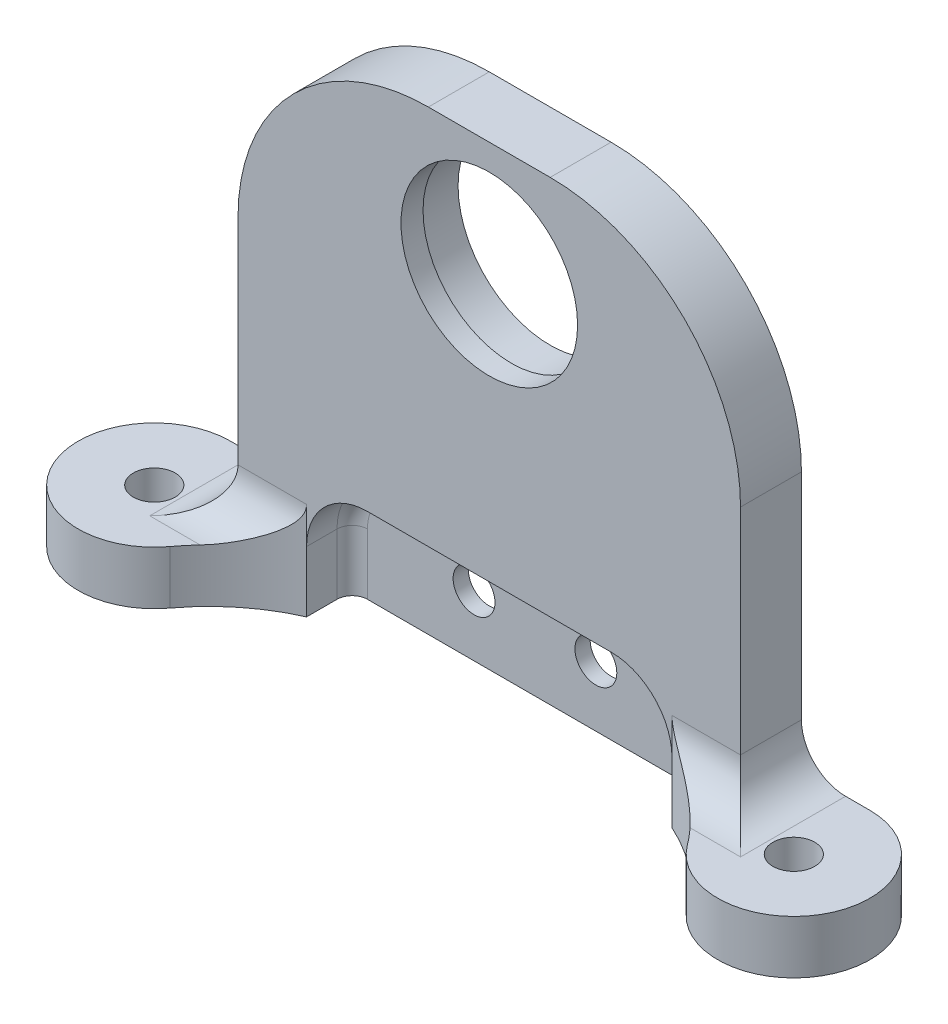
SolidWorks part; units mm, degrees
ref_plane "Front Plane" through (0, 0, 0) normal (0, 0, 1) x (1, 0, 0)
ref_plane "Top Plane" through (0, 0, 0) normal (0, 1, 0) x (1, 0, 0)
ref_plane "Right Plane" through (0, 0, 0) normal (1, 0, 0) x (0, 0, -1)
sketch "Sketch1" plane through (0, 0, 0) normal (0, 0, 1) x (1, 0, 0)
  line L1 (0, 15) -> (33, 15)
  line L2 (0, 15) -> (0, -51)
  line L3 (0, -51) -> (33, -51)
  line L4 (33, 15) -> (33, -51)
  point P5 (0, 0)
  dimension "D1" = 33
  dimension "D2" = 66
  dimension "D4" = 15
extrude "Boss-Extrude1" add sketch "Sketch1" along normal blind 8 separate body
sketch "Sketch3" plane through (0, 0, 8) normal (0, 0, 1) x (1, 0, 0)
  line L0 (0, 15) -> (0, -51) construction
  line L1 (33, 15) -> (0, 15) construction
  line L2 (9.5671, -23.097) -> (0, 0) construction
  line L3 (-17.5, 0) -> (-32.5, 0) construction
  line L4 (33, -51) -> (33, 15) construction
  line L5 (0, -51) -> (33, -51) construction
  circle A0 centre (25, -20) radius 2.75 construction
  circle A1 centre (0, 0) radius 11.6
  arc A2 (-17.5, 0) -> (6.697, -16.1679) centre (0, 0) ccw construction
  arc A3 (-32.5, 0) -> (12.4372, -30.0261) centre (0, 0) ccw construction
  arc A4 (12.4372, -30.0261) -> (6.697, -16.1679) centre (9.5671, -23.097) ccw construction
  dimension "D1" = 5.5
  dimension "D2" = 23.2
  dimension "D4" = 35
  dimension "D5" = 65
  dimension "D3" = 15
  dimension "D6" = 22.5
  dimension "D7" = 8
  dimension "D8" = 31
extrude "Cut-Extrude1" cut sketch "Sketch3" against normal through all
sketch "Sketch6" plane through (0, 0, 0) normal (0, 0, -1) x (-1, 0, 0)
  circle A0 centre (0, 0) radius 12.1
  dimension "D1" = 24.2
extrude "Cut-Extrude2" cut sketch "Sketch6" against normal blind 5.1
fillet "Fillet4" radius 25 1 edges at (33, 15, 4)
sketch "Sketch10" plane through (0, -51, 0) normal (0, -1, 0) x (1, 0, 0)
  line L0 (42, 0) -> (32, 0)
  line L1 (0, 0) -> (33, 0) construction
  line L2 (32, 10) -> (32, 0)
  line L3 (33, 8) -> (33, 0) construction
  arc A0 (42, 0) -> (32, 10) centre (42, 10) ccw
  circle A1 centre (42, 10) radius 2.75
  dimension "D1" = 5.5
  dimension "D2" = 20
  dimension "D3" = 1
extrude "Boss-Extrude4" add sketch "Sketch10" against normal blind 7
sketch "Sketch11" plane through (0, 0, 8) normal (0, 0, 1) x (1, 0, 0)
  line L1 (0, -51) -> (24, -51)
  line L2 (0, -51) -> (0, -35)
  line L3 (0, -35) -> (16, -35)
  line L4 (24, -51) -> (24, -43)
  arc A0 (16, -35) -> (24, -43) centre (16, -43) cw
  dimension "D1" = 8
  dimension "D2" = 16
  dimension "D3" = 24
extrude "Cut-Extrude3" cut sketch "Sketch11" against normal blind 6
sketch "Sketch12" plane through (0, 0, 2) normal (0, 0, 1) x (1, 0, 0)
  line L0 (8, -43) -> (0, -43) construction
  line L1 (0, -35) -> (0, -51) construction
  circle A0 centre (8, -43) radius 2.75
  dimension "D1" = 5.5
  dimension "D2" = 8
extrude "Cut-Extrude4" cut sketch "Sketch12" against normal blind 6
fillet "Fillet7" radius 2 3 edges at (24, -47, 2) (8, -35, 2) (21.6569, -37.3431, 2)
fillet "Fillet5" radius 25 1 edges at (32, -47.5, 8)
fillet "Fillet6" radius 5.8 2 edges at (33, -44, 4) (28.5, -44, 8)
mirror "Mirror1" about plane through (0, 15, 8) normal (1, 0, 0) of bodies 111 105
ref_plane "Mid Plane" through (0, 0, 0) normal (1, 0, 0) x (0, 0, -1)
